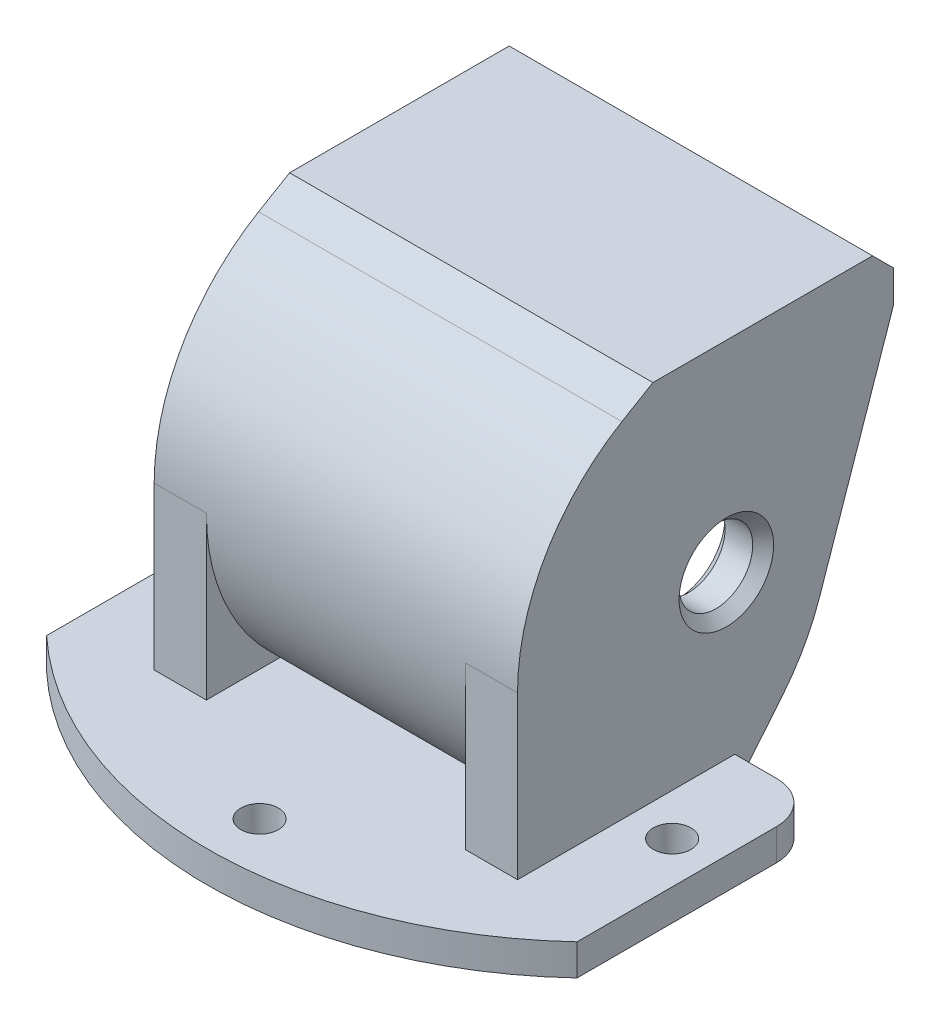
SolidWorks part; units mm, degrees
ref_plane "Front Plane" through (0, 0, 0) normal (0, 0, 1) x (1, 0, 0)
ref_plane "Top Plane" through (0, 0, 0) normal (0, 1, 0) x (1, 0, 0)
ref_plane "Right Plane" through (0, 0, 0) normal (1, 0, 0) x (0, 0, -1)
sketch "Sketch1" plane through (0, 0, 0) normal (1, 0, 0) x (0, 0, -1)
  line L0 (0, 17.5) -> (0, -17.5) construction
  line L1 (0, 17.5) -> (-10, 17.5)
  line L2 (10, 17.5) -> (10, -17.5) construction
  line L3 (0, -17.5) -> (-10, -17.5)
  line L4 (-10, 17.5) -> (-10, -17.5) construction
  line L5 (0, 0) -> (10, 0) construction
  line L6 (0, 0) -> (-10, 0) construction
  line L7 (0, 0) -> (-10, 0) construction
  line L8 (-10, 0) -> (-20, 0) construction
  arc A0 (0, -17.5) -> (0, 17.5) centre (-10.3125, 0) ccw
  arc A1 (-10, 17.5) -> (-10, -17.5) centre (0.3125, 0) ccw
  dimension "D3" = 20
  dimension "D1" = 35
extrude "Boss-Extrude1" add sketch "Sketch1" against normal mid plane 34.8
sketch "Sketch2" plane through (0, 0, 0) normal (1, 0, 0) x (0, 0, -1)
  line L0 (0, 17.5) -> (-10, 17.5) construction
  line L1 (-10, -17.5) -> (0, -17.5) construction
  line L2 (-16, 0) -> (-20, 0) construction
  line L4 (-10, -17.5) -> (0, -17.5)
  line L5 (0, 17.5) -> (-10, 17.5)
  line L6 (-6, -17.5) -> (0, -17.5)
  line L7 (0, 17.5) -> (-6, 17.5)
  arc A0 (-6, 17.5) -> (-6, -17.5) centre (4.3125, 0) ccw
  arc A1 (-10, 17.5) -> (-10, -17.5) centre (0.3125, 0) ccw construction
  arc A4 (-10, 17.5) -> (-10, -17.5) centre (0.3125, 0) ccw
  arc A5 (0, -17.5) -> (0, 17.5) centre (-10.3125, 0) ccw
  arc A7 (0, -17.5) -> (0, 17.5) centre (-10.3125, 0) ccw
  dimension "D1" = 0
  dimension "D2" = 4
extrude "Cut-Extrude1" cut sketch "Sketch2" along normal mid plane 25.5
sketch "Sketch3" plane through (0, 0, 0) normal (1, 0, 0) x (0, 0, -1)
  line L0 (-9.5, -17.5) -> (-9.5, -24)
  line L1 (-10, -17.5) -> (0, -17.5) construction
  line L2 (-0.5, -24) -> (-0.5, -17.5)
  line L3 (-0.5, -17.5) -> (-9.5, -17.5)
  line L4 (-5, -28.5) -> (-5, -17.5) construction
  arc A0 (-9.5, -24) -> (-0.5, -24) centre (-5, -24) ccw
  dimension "D1" = 9
  dimension "D2" = 6.5
extrude "Boss-Extrude2" add sketch "Sketch3" along normal mid plane 10
sketch "Sketch4" plane through (17.4, 0, 0) normal (1, 0, 0) x (0, 0, -1)
  line L0 (-13.4374, -9.8761) -> (0.9816, -18.201)
  line L1 (0.8089, -18.5) -> (-8.303, -18.5)
  line L4 (-13.4374, -9.8761) -> (-17.4374, -9.8761)
  line L5 (0.8089, -18.5) -> (0.9816, -18.201)
  line L8 (0, 0) -> (14.9634, 0.0217) construction
  line L9 (14.9634, 0.0217) -> (14.9855, -15.25) construction
  line L10 (69.9999, 0.1014) -> (0, 0) construction
  line L12 (-10, -17.5) -> (-8.303, -18.5)
  line L13 (0.9816, -18.201) -> (8.6174, -4.9753) construction
  line L14 (0, 0) -> (8.6174, -4.9753) construction
  line L15 (0, 0) -> (-8.348, 0) construction
  line L16 (-10, -17.5) -> (0, -17.5) construction
  arc A0 (-10, 17.5) -> (-10, -17.5) centre (0.3125, 0) ccw construction
  arc A2 (-6, 17.5) -> (-6, -17.5) centre (4.3125, 0) ccw construction
  arc A3 (-6, 17.5) -> (-6, -17.5) centre (4.3125, 0) ccw construction
  arc A4 (-17.4374, -9.8761) -> (-10, -17.5) centre (0.3125, 0) ccw
  dimension "D1" = 30
  dimension "D2" = 0.299
  dimension "D3" = 1
extrude "Boss-Extrude3" add sketch "Sketch4" against normal up to surface (34.8 mm away) up to face at (-17.4, 0, 5)
sketch "Sketch5" plane through (17.4, 0, 0) normal (1, 0, 0) x (0, 0, -1)
  line L4 (-8.303, -18.5) -> (0.8089, -18.5) construction
  line L5 (5.426, -12.8412) -> (0.8089, -18.5)
  line L6 (0.8089, -18.5) -> (0.9816, -18.201) construction
  line L7 (0.8089, -18.5) -> (-1.1911, -18.5)
  line L8 (-1.1911, -18.5) -> (-1.1911, -17.5)
  line L9 (-1.1911, -17.5) -> (5.426, -12.8412)
  arc A3 (0, -17.5) -> (0, 17.5) centre (-10.3125, 0) ccw construction
  dimension "D1" = 1
  dimension "D2" = 2
extrude "Boss-Extrude4" add sketch "Sketch5" against normal up to surface (4.65 mm away) up to face at (12.75, -1.6725, 3.0481)
sketch "Sketch6" plane through (-17.4, 0, 0) normal (-1, 0, 0) x (0, 0, 1)
  line L2 (-5.426, -12.8412) -> (-0.8089, -18.5)
  line L3 (-5.426, -12.8412) -> (-0.8089, -18.5)
  line L4 (-0.8089, -18.5) -> (1.1911, -18.5)
  line L5 (-0.8089, -18.5) -> (1.1911, -18.5)
  line L12 (1.1911, -18.5) -> (1.1911, -17.5)
  line L13 (1.1911, -18.5) -> (1.1911, -17.5)
  line L14 (1.1911, -17.5) -> (-5.426, -12.8412)
  line L15 (1.1911, -17.5) -> (-5.426, -12.8412)
  dimension "D1" = 0
extrude "Boss-Extrude5" add sketch "Sketch6" against normal up to surface (4.65 mm away) up to face at (-12.75, -1.6725, 3.0481)
sketch "Sketch7" plane through (17.4, 0, 0) normal (1, 0, 0) x (0, 0, -1)
  line L0 (-10, 17.5) -> (-7.0303, 19.25)
  line L1 (-7.0303, 19.25) -> (16, 19.25)
  line L2 (16, 19.25) -> (16, 14.1219)
  line L3 (0, 0) -> (1.3291, 15.192) construction
  line L4 (3.1052, 15.25) -> (-13.1052, 15.25)
  line L6 (0, 0) -> (0, 15.25) construction
  line L7 (69.7336, -6.1009) -> (0, 0) construction
  line L8 (86.3842, 7.7506) -> (31.7938, 12.5267) construction
  line L9 (0, 17.5) -> (-10, 17.5) construction
  line L10 (3.1052, 15.25) -> (16, 14.1219)
  line L11 (0, 17.5) -> (-10, 17.5) construction
  line L13 (10, 0) -> (10, 11.0966) construction
  line L14 (0, 0) -> (69.7336, 0) construction
  arc A0 (-10, 17.5) -> (-10, -17.5) centre (0.3125, 0) ccw construction
  arc A1 (-10, 17.5) -> (-13.1052, 15.25) centre (0.3125, 0) ccw
  arc A3 (5.426, -12.8412) -> (0, 17.5) centre (-10.3125, 0) ccw construction
  dimension "D1" = 5
  dimension "D2" = 4
  dimension "D3" = 6
extrude "Boss-Extrude6" add sketch "Sketch7" against normal up to surface (34.8 mm away) up to face at (-17.4, -5.1825, 4.1831)
sketch "Sketch8" plane through (17.4, 0, 0) normal (1, 0, 0) x (0, 0, -1)
  line L0 (16, 14.1219) -> (8.9027, -6.5858)
  line L2 (3.1052, 15.25) -> (16, 14.1219)
  arc A0 (5.426, -12.8412) -> (3.1052, 15.25) centre (-10.3125, 0) ccw construction
  arc A1 (8.9027, -6.5858) -> (3.1052, 15.25) centre (-10.3125, 0) ccw
extrude "Boss-Extrude7" add sketch "Sketch8" against normal up to surface (4.65 mm away) up to face at (12.75, -4.6143, 1.8315)
sketch "Sketch9" plane through (-17.4, 0, 0) normal (-1, 0, 0) x (0, 0, 1)
  line L2 (-16, 14.1219) -> (-8.9027, -6.5858)
  line L3 (-3.1052, 15.25) -> (-16, 14.1219)
  line L4 (-16, 14.1219) -> (-8.9027, -6.5858)
  line L5 (-3.1052, 15.25) -> (-16, 14.1219)
  arc A1 (-3.1052, 15.25) -> (-8.9027, -6.5858) centre (10.3125, 0) ccw
  arc A2 (-3.1052, 15.25) -> (-8.9027, -6.5858) centre (10.3125, 0) ccw
  dimension "D1" = 0
extrude "Boss-Extrude8" add sketch "Sketch9" against normal up to surface (4.65 mm away) up to face at (-12.75, -4.6143, 1.8315)
chamfer "Chamfer2" distance 2 angle 45 1 edges at (0, 19.25, -16)
sketch "Sketch10" plane through (17.4, 0, 0) normal (1, 0, 0) x (0, 0, -1)
  circle A0 centre (0, 0) radius 3.175 construction
  circle A1 centre (0, 0) radius 3.525
  dimension "D1" = 6.35
  dimension "D2" = 0.35
extrude "Cut-Extrude2" cut sketch "Sketch10" against normal through all
sketch "Sketch11" plane through (0, 0, 0) normal (1, 0, 0) x (0, 0, -1)
  line L3 (-9.5, -17.5) -> (-9.5, -24)
  line L4 (-0.5, -24) -> (-0.5, -17.5)
  line L5 (-0.5, -17.5) -> (-9.5, -17.5)
  line L6 (-9.5, -17.5) -> (-9.5, -24)
  line L7 (-0.5, -24) -> (-0.5, -17.5)
  line L8 (-0.5, -17.5) -> (-9.5, -17.5)
  arc A1 (-9.5, -24) -> (-0.5, -24) centre (-5, -24) ccw
  arc A2 (-9.5, -24) -> (-0.5, -24) centre (-5, -24) ccw
  dimension "D1" = 0
extrude "Cut-Extrude3" cut sketch "Sketch11" against normal mid plane 0.762
chamfer "Chamfer3" [suppressed] distance 5 angle 45
sketch "Sketch12" plane through (0, -18.5, 0) normal (0, -1, 0) x (1, 0, 0)
  line L0 (-17.4, -0.8089) -> (-21.4, -0.8089)
  line L2 (21.4, -0.8089) -> (17.4, -0.8089)
  line L4 (-25.4, 22.303) -> (25.4, 22.303) construction
  line L8 (-25.4, 3.1911) -> (-25.4, 22.303)
  line L9 (25.4, 22.303) -> (25.4, 3.1911)
  line L10 (-17.4, 8.303) -> (-25.4, 8.303) construction
  line L11 (0, 22.303) -> (0, 32.303) construction
  line L12 (-17.4, -0.8089) -> (-17.4, 8.303) construction
  line L13 (17.4, 8.303) -> (25.4, 8.303) construction
  line L14 (17.4, 8.303) -> (17.4, -0.8089) construction
  line L15 (-17.4, -0.8089) -> (-17.4, 8.303)
  line L16 (17.4, 8.303) -> (17.4, -0.8089)
  line L17 (17.4, 8.303) -> (-17.4, 8.303)
  arc A0 (-21.4, -0.8089) -> (-25.4, 3.1911) centre (-21.4, 3.1911) cw
  arc A1 (25.4, 3.1911) -> (21.4, -0.8089) centre (21.4, 3.1911) cw
  arc A2 (-25.4, 22.303) -> (25.4, 22.303) centre (0, -4.955) cw
  dimension "D2" = 4
  dimension "D1" = 8
  dimension "D3" = 10
  dimension "D4" = 14
extrude "Boss-Extrude9" add sketch "Sketch12" against normal blind 3
sketch "Sketch13" plane through (-17.4, 0, 0) normal (-1, 0, 0) x (0, 0, 1)
  line L0 (20, -15.5) -> (12.8156, -15.5) construction
  line L1 (20, -15.5) -> (20, 0)
  line L3 (12.8156, -15.5) -> (12.8156, -23.5)
  line L4 (12.8156, -23.5) -> (20, -23.5)
  line L5 (20, -23.5) -> (20, -15.5)
  line L6 (22.303, -18.5) -> (3.1911, -18.5) construction
  arc A0 (20, 0) -> (12.8156, -15.5) centre (-0.3125, 0) cw
  arc A1 (12.8156, -15.5) -> (10, 17.5) centre (-0.3125, 0) ccw construction
  dimension "D1" = 5
extrude "Boss-Extrude10" add sketch "Sketch13" against normal blind 5
mirror "Mirror1" about plane through (0, 0, 0) normal (1, 0, 0) of "Boss-Extrude10"
hole_wizard "M3 Clearance Hole1" positions "Sketch14" profile "Sketch15" hole size "M3" standard "ANSI Metric" end condition through all
sketch "Sketch14" plane through (0, -15.5, 0) normal (0, 1, 0) x (1, 0, 0)
  line L3 (0, -27.303) -> (0, -32.303) construction
  line L4 (-21.4, 0.8089) -> (-21.4, -9.1911) construction
  line L6 (21.4, 0.8089) -> (21.4, -9.1911) construction
  arc A1 (-25.4, -22.303) -> (25.4, -22.303) centre (0, 4.955) ccw construction
  point P10 (0, -27.303)
  point P34 (-21.4, -9.1911)
  point P36 (21.4, -9.1911)
  dimension "D1" = 5
  dimension "D2" = 10
sketch "Sketch15" plane through (0, -15.5, 27.303) normal (1, 0, 0) x (0, 0, 1)
  line L0 (0, 0) -> (0, 13)
  line L1 (0, 13) -> (1.8, 13)
  line L2 (1.8, 13) -> (1.8, 0)
  line L5 (1.8, 0) -> (0, 0)
  line L11 (0, -6.35) -> (0, 107.95) construction
  dimension "Thru Hole Dia." = 3.6
  dimension "Thru Hole Depth" = 13
hole_wizard "M3 Clearance Hole2" positions "Sketch16" profile "Sketch17" hole size "M3" standard "ANSI Metric" end condition through all
sketch "Sketch16" plane through (5, 0, 0) normal (1, 0, 0) x (0, 0, -1)
  point P0 (-5, -24)
sketch "Sketch17" plane through (5, -24, 5) normal (0, 1, 0) x (0, 0, -1)
  line L0 (0, 0) -> (0, 30.4)
  line L1 (0, 30.4) -> (1.8, 30.4)
  line L2 (1.8, 30.4) -> (1.8, 0)
  line L5 (1.8, 0) -> (0, 0)
  line L11 (0, -6.35) -> (0, 107.95) construction
  dimension "Thru Hole Dia." = 3.6
  dimension "Thru Hole Depth" = 30.4
chamfer "Chamfer5" distance 1 angle 45 4 edges at (17.4, 0, -3.525) (-12.75, 0, -3.525) (-17.4, 0, -3.525) (12.75, 0, -3.525)
sketch "Sketch18" plane through (0, 0, 0) normal (1, 0, 0) x (0, 0, -1)
  line L0 (0.9816, -18.201) -> (-13.4374, -9.8761)
  line L1 (-0.2321, -17.5002) -> (-13.4374, -9.8761) construction
  line L2 (-11.421, -18.5) -> (-0.5, -18.5) construction
  line L3 (-3.1911, -18.5) -> (-22.303, -18.5) construction
  line L4 (-0.5, -18.5) -> (1.4995, -18.5)
  line L5 (1.4995, -18.5) -> (-0.2321, -17.5002)
  arc A0 (-0.2321, -17.5002) -> (-0.5, -18.5) centre (-0.5, -17.9642) cw
extrude "Cut-Extrude4" cut sketch "Sketch18" against normal up to surface and the other way up to surface up to face at (-12.75, 0, -4.525) other way up to face at (12.75, 0, -4.525)
chamfer "Chamfer6" distance 1 angle 45 8 edges at (-14.9, -23.5, 20) (-12.4, -23.5, 16.4078) (-14.9, -23.5, 12.8156) (-17.4, -23.5, 16.4078) (14.9, -23.5, 12.8156) (12.4, -23.5, 16.4078) (14.9, -23.5, 20) (17.4, -23.5, 16.4078)
